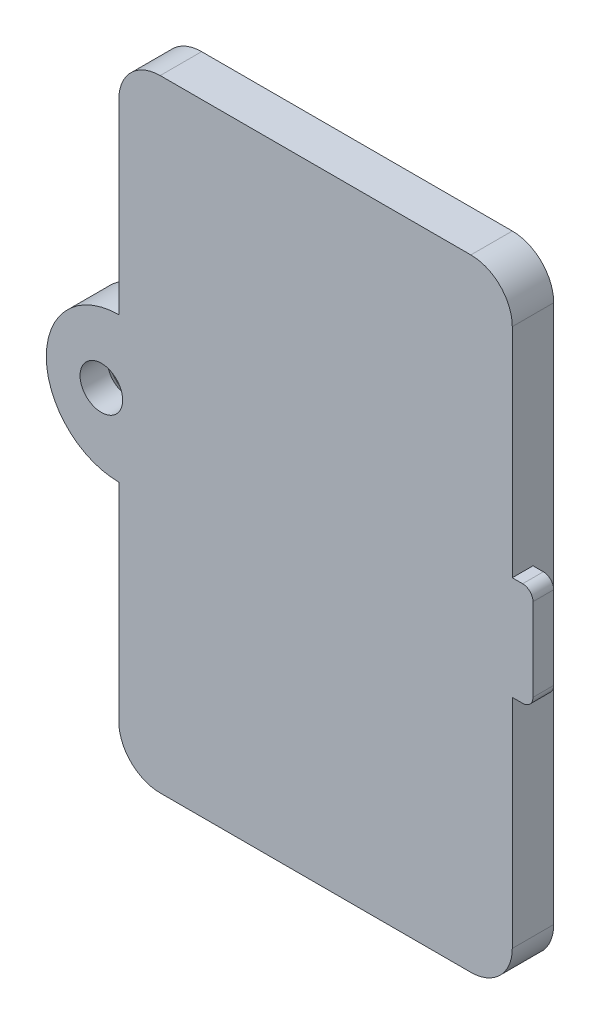
SolidWorks part; units mm, degrees
ref_plane "Front Plane" through (0, 0, 0) normal (0, 0, 1) x (1, 0, 0)
ref_plane "Top Plane" through (0, 0, 0) normal (0, 1, 0) x (1, 0, 0)
ref_plane "Right Plane" through (0, 0, 0) normal (1, 0, 0) x (0, 0, -1)
sketch "Sketch1" plane through (0, 0, 0) normal (0, 0, 1) x (1, 0, 0)
  line L5 (-70.7652, -17.59) -> (-51.7652, -17.59)
  line L7 (-70.7652, -47.59) -> (-51.7652, -47.59)
  line L9 (-70.7652, -17.59) -> (-70.7652, -28.59)
  line L10 (-70.7652, -47.59) -> (-70.7652, -35.59)
  line L16 (-51.7652, -17.59) -> (-51.7652, -47.59)
  arc A0 (-70.7652, -28.59) -> (-70.7652, -35.59) centre (-70.7652, -32.09) ccw
  dimension "D6" = 3.5
  dimension "D1" = 30
  dimension "D2" = 19
  dimension "D3" = 19
  dimension "D4" = 11
  dimension "D5" = 12
  dimension "D7" = 17.59
  dimension "D8" = 51.7652
extrude "Boss-Extrude1" add sketch "Sketch1" along normal blind 1 and the other way blind 1
sketch "Sketch2" plane through (0, 0, 1) normal (0, 0, 1) x (1, 0, 0)
  line L0 (-51.7652, -17.59) -> (-70.7652, -17.59) construction
  line L1 (-51.7652, -30.09) -> (-50.7652, -30.09)
  line L2 (-51.7652, -30.09) -> (-51.7652, -35.09)
  line L3 (-51.7652, -35.09) -> (-50.7652, -35.09)
  line L4 (-50.7652, -30.09) -> (-50.7652, -35.09)
  line L5 (-51.7652, -47.59) -> (-51.7652, -17.59) construction
  point P4 (-50.7652, -32.59)
  dimension "D1" = 15
  dimension "D2" = 1
  dimension "D3" = 5
  dimension "D4" = 0
extrude "Boss-Extrude3" add sketch "Sketch2" against normal blind 1
fillet "Fillet1" radius 2 4 edges at (-70.7652, -17.59, 0) (-51.7652, -17.59, 0) (-51.7652, -47.59, 0) (-70.7652, -47.59, 0)
fillet "Fillet2" radius 0.5 2 edges at (-50.7652, -30.09, 0.5) (-50.7652, -35.09, 0.5)
hole_wizard "CSK for #1 Flat Head Machine Screw (100)1" positions "3DSketch1" profile "Sketch3" countersink size "#1" standard "ANSI Inch"
sketch3d "3DSketch1"
  point P0 (-71.6064, -32.0687, -1)
sketch "Sketch3" plane through (-71.6064, -32.0687, -1) normal (1, 0, 0) x (0, 1, 0)
  line L0 (0, 0) -> (0, 6)
  line L1 (0, 6) -> (1.0287, 5.3819)
  line L2 (1.0287, 5.3819) -> (1.0287, 0.6927)
  line L3 (1.0287, 0.6927) -> (1.8542, 0)
  line L5 (1.8542, 0) -> (0, 0)
  line L6 (-1.0287, 0.6927) -> (-1.8542, 0) construction
  line L10 (0, 6) -> (-1.0287, 5.3819) construction
  line L11 (0, -6.35) -> (0, 107.95) construction
  dimension "Hole Dia." = 2.0574
  dimension "Hole Depth" = 6
  dimension "Near C'Sink Dia." = 3.7084
  dimension "Near C'Sink Angle" = 100
  dimension "Drill Angle" = 118
